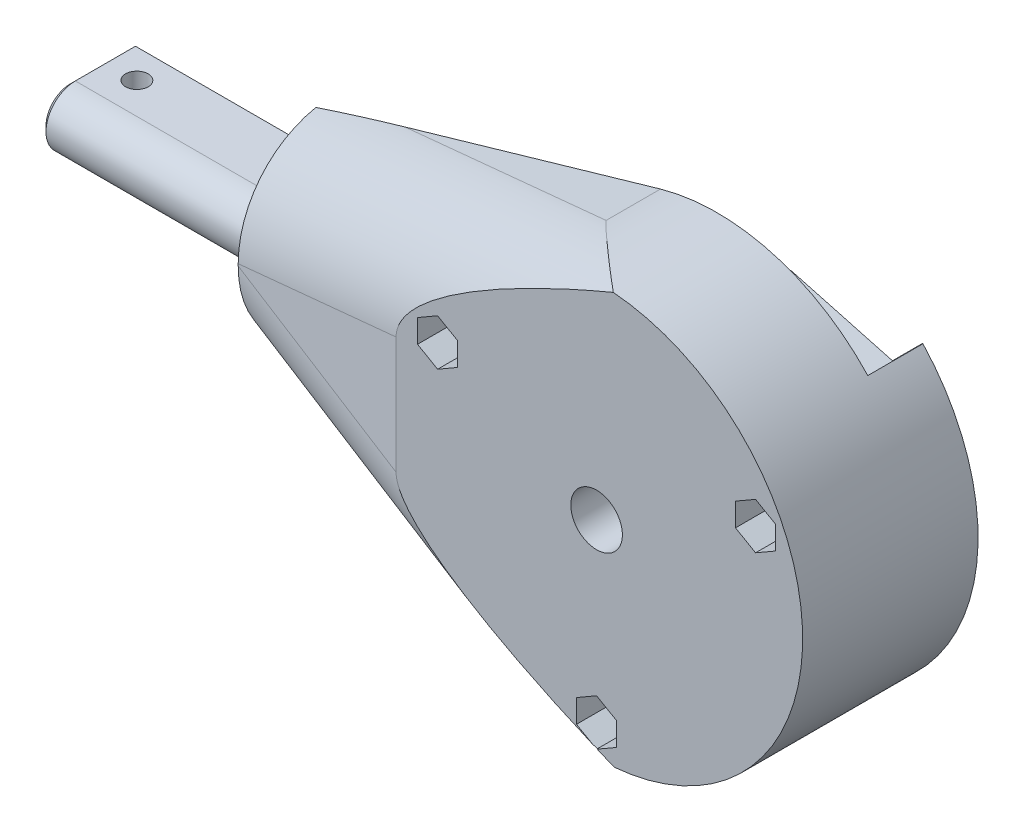
SolidWorks part; units mm, degrees
ref_plane "Plano frontal" through (0, 0, 0) normal (0, 0, 1) x (1, 0, 0)
ref_plane "Plano superior" through (0, 0, 0) normal (0, 1, 0) x (1, 0, 0)
ref_plane "Plano direito" through (0, 0, 0) normal (1, 0, 0) x (0, 0, -1)
sketch "Esboço1" plane through (0, 0, 0) normal (0, 0, 1) x (1, 0, 0)
  line L4 (-219.2737, 94) -> (-235.9914, 122.9559)
  line L5 (-288.8814, 87.15) -> (-288.8814, 80)
  line L6 (-288.8814, 80) -> (-220.128, 60.4494)
  line L9 (-288.8814, 80) -> (-220.128, 60.4494)
  line L16 (-178.8471, 128.0209) -> (-198.4891, 94)
  line L18 (-235.9914, 122.9559) -> (-288.8814, 107.9162)
  line L41 (-288.8814, 119.6353) -> (-288.8814, 80)
  line L53 (-288.8814, 100.0176) -> (-288.8814, 119.2633) construction
  line L54 (-288.8814, 119.6353) -> (-220.128, 139.5506)
  line L55 (-290.8814, 100.85) -> (-335.8814, 100.85)
  line L57 (-335.8814, 100.85) -> (-336.8814, 99.85)
  line L59 (-336.8814, 99.85) -> (-336.8814, 90.15)
  line L61 (-336.8814, 90.15) -> (-335.8814, 89.15)
  line L63 (-335.8814, 89.15) -> (-290.8814, 89.15)
  line L65 (-288.8814, 107.9162) -> (-288.8814, 102.85)
  line L112 (-178.7691, 127.9998) -> (-178.8471, 128.0209)
  arc A3 (-220.128, 60.4494) -> (-220.128, 139.5506) centre (-208.8814, 100) ccw
  arc A14 (-220.128, 60.4494) -> (-178.7691, 127.9998) centre (-208.8814, 100) ccw
  arc A15 (-219.2737, 94) -> (-198.4891, 94) centre (-208.8814, 100) ccw
  arc A19 (-288.8814, 87.15) -> (-290.8814, 89.15) centre (-290.8814, 87.15) ccw
  arc A21 (-290.8814, 100.85) -> (-288.8814, 102.85) centre (-290.8814, 102.85) ccw
  ellipse E1 centre (-265.5978, 105.828) end of major axis (-169.5588, 133.1375) minor radius 20 (-271.0682, 125.0654) -> (-288.8814, 119.6353) ccw construction
  dimension "D1" = 0
extrude "Ressalto-extrusão1" add sketch "Esboço1" along normal up to surface (35 mm away)
chamfer "Chanfro1" distance 40 angle 12 1 edges at (-288.8814, 99.8176, 35) first distance on face at (-241.4134, 99.9088, 35)
fillet "Filete2" radius 20 2 edges at (-268.8814, 125.4285, 30.7489) (-268.8814, 74.3128, 30.7489)
ref_axis "Eixo1" through (-208.8814, 100, 35) along (0, 0, -1)
sketch "Esboço6" plane through (0, 0, 0) normal (0, 0, -1) x (-1, 0, 0)
  line L0 (219.2737, 94) -> (245.2234, 138.9462)
  line L1 (198.4891, 94) -> (172.5394, 138.9462)
  line L2 (208.8814, 100) -> (208.8814, 151.5246) construction
  line L3 (172.5394, 138.9462) -> (245.2234, 138.9462)
  arc A0 (198.4891, 94) -> (219.2737, 94) centre (208.8814, 100) ccw
  dimension "D1" = 24
  dimension "D2" = 30
extrude "Corte-extrusão2" cut sketch "Esboço6" against normal blind 6
sketch "Esboço7" plane through (0, 0, 0) normal (0, 0, -1) x (-1, 0, 0)
  line L0 (179.1715, 139.1131) -> (295.6181, 106.0005)
  line L6 (295.6181, 106.0005) -> (295.6181, 136.4235)
  line L7 (295.6181, 136.4235) -> (188.9482, 165.3081)
  line L8 (188.9482, 165.3081) -> (179.1715, 139.1131)
  line L14 (288.8814, 107.9162) -> (235.9914, 122.9559) construction
extrude "Corte-extrusão3" cut sketch "Esboço7" against normal blind 11
chamfer "Chanfro2" distance 10 angle 31 1 edges at (-189.3926, 136.2067, 8.5) first distance on face at (-238.0885, 122.3596, 5.6667)
sketch "Esboço8" plane through (-288.8814, 0, 0) normal (-1, 0, 0) x (0, 0, 1)
  line L6 (0, 100.85) -> (12, 100.85)
  line L7 (12, 89.15) -> (0, 89.15)
  line L9 (0, 107.9162) -> (0, 80) construction
  line L10 (0, 100.85) -> (0, 89.15)
  arc A2 (12, 89.15) -> (12, 100.85) centre (12, 95) ccw
  dimension "D1" = 12
extrude "Ressalto-extrusão2" add sketch "Esboço8" along normal blind 48
chamfer "Chanfro3" distance 1 angle 45 3 edges at (-336.8814, 89.15, 6) (-336.8814, 95, 17.85) (-336.8814, 100.85, 6)
fillet "Filete3" radius 2 3 edges at (-288.8814, 89.15, 6) (-288.8814, 95, 17.85) (-288.8814, 100.85, 6)
sketch "Esboço9" plane through (0, 100.85, 0) normal (0, 1, 0) x (1, 0, 0)
  circle A0 centre (-329.8463, -5.7511) radius 2.25
  circle A1 centre (-297.91, -5.7511) radius 2.25
extrude "Corte-extrusão4" cut sketch "Esboço9" against normal through all
sketch "Esboço10" plane through (0, 0, 0) normal (0, 0, -1) x (-1, 0, 0)
  circle A0 centre (208.8814, 100) radius 5.15
  dimension "D1" = 10.3
extrude "Corte-extrusão5" cut sketch "Esboço10" against normal through all
sketch "Esboço12" plane through (0, 0, 35) normal (0, 0, 1) x (1, 0, 0)
  line L1 (-240.5998, 119.4155) -> (-244.5998, 117.1061)
  line L2 (-244.5998, 117.1061) -> (-244.5998, 112.4873)
  line L3 (-244.5998, 112.4873) -> (-240.5998, 110.1779)
  line L4 (-240.5998, 110.1779) -> (-236.5998, 112.4873)
  line L5 (-236.5998, 112.4873) -> (-236.5998, 117.1061)
  line L6 (-236.5998, 117.1061) -> (-240.5998, 119.4155)
  line L7 (-208.8814, 69.6188) -> (-212.8814, 67.3094)
  line L8 (-212.8814, 67.3094) -> (-212.8814, 62.6906)
  line L9 (-212.8814, 62.6906) -> (-208.8814, 60.3812)
  line L10 (-208.8814, 60.3812) -> (-204.8814, 62.6906)
  line L11 (-204.8814, 62.6906) -> (-204.8814, 67.3094)
  line L12 (-204.8814, 67.3094) -> (-208.8814, 69.6188)
  line L13 (-177.163, 119.4155) -> (-181.163, 117.1061)
  line L14 (-181.163, 117.1061) -> (-181.163, 112.4873)
  line L15 (-181.163, 112.4873) -> (-177.163, 110.1779)
  line L16 (-177.163, 110.1779) -> (-173.163, 112.4873)
  line L17 (-173.163, 112.4873) -> (-173.163, 117.1061)
  line L18 (-173.163, 117.1061) -> (-177.163, 119.4155)
  circle A0 centre (-240.5998, 114.7967) radius 4 construction
  circle A1 centre (-208.8814, 65) radius 4 construction
  circle A2 centre (-177.163, 114.7967) radius 4 construction
  dimension "D1" = 8
extrude "Corte-extrusão7" cut sketch "Esboço12" against normal blind 10
sketch "Esboço13" plane through (0, 0, 25) normal (0, 0, 1) x (1, 0, 0)
  circle A0 centre (-177.163, 114.7967) radius 2.25
  circle A1 centre (-208.8814, 65) radius 2.25
  circle A2 centre (-240.5998, 114.7967) radius 2.25
  dimension "D1" = 4.5
extrude "Corte-extrusão8" cut sketch "Esboço13" against normal through all
